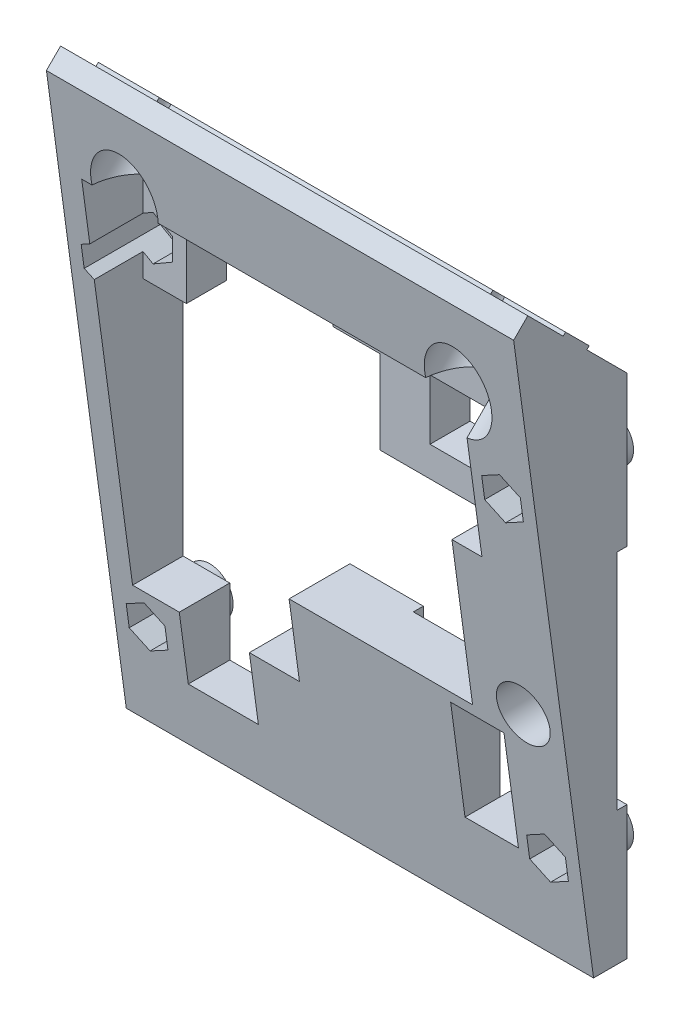
SolidWorks part; units mm, degrees
ref_plane "前视基准面" through (0, 0, 0) normal (0, 0, 1) x (1, 0, 0)
ref_plane "上视基准面" through (0, 0, 0) normal (0, 1, 0) x (1, 0, 0)
ref_plane "右视基准面" through (0, 0, 0) normal (1, 0, 0) x (0, 0, -1)
sketch "草图1" plane through (0, 0, 0) normal (1, 0, 0) x (0, 0, -1)
  line L0 (0, 0) -> (0, 76)
  line L1 (0, 76) -> (-14.8492, 90.8492)
  line L3 (-5, 0) -> (0, 0)
  line L4 (-14.8492, 90.8492) -> (-16.9706, 88.7279)
  line L5 (-16.9706, 88.7279) -> (-5, 0)
  dimension "D1" = 5
  dimension "D2" = 135
  dimension "D3" = 21
  dimension "D4" = 76
  dimension "D5" = 3
extrude "凸台-拉伸1" add sketch "草图1" along normal blind 90
sketch "草图2" plane through (0, 0, 0) normal (0, 0, -1) x (-1, 0, 0)
  line L0 (-90, 64) -> (0, 64) construction
  line L1 (-90, 0) -> (-90, 76) construction
  line L2 (0, 0) -> (0, 76) construction
  line L3 (-90, 14) -> (0, 14) construction
  line L4 (-75, 76) -> (-75, 0) construction
  line L5 (-90, 76) -> (0, 76) construction
  line L6 (-90, 0) -> (0, 0) construction
  line L7 (-15, 76) -> (-15, 0) construction
  circle A0 centre (-75, 64) radius 1.75
  circle A2 centre (-15, 64) radius 1.75
  circle A3 centre (-15, 14) radius 1.75
  circle A4 centre (-75, 14) radius 1.75
  dimension "D5" = 3.5
  dimension "D1" = 15
  dimension "D2" = 60
  dimension "D3" = 50
  dimension "D4" = 12
extrude "切除-拉伸1" cut sketch "草图2" against normal through all
sketch "草图3" plane through (0, 0, 0) normal (0, 0, -1) x (-1, 0, 0)
  line L0 (-90, 0) -> (-90, 76) construction
  line L1 (-38.5, 58) -> (-13.5, 58)
  line L2 (-38.5, 58) -> (-38.5, 19)
  line L3 (-38.5, 19) -> (-13.5, 19)
  line L4 (-13.5, 58) -> (-13.5, 19)
  line L5 (-20.5, 19) -> (-31, 19)
  line L6 (-20.5, 19) -> (-20.5, 9)
  line L7 (-20.5, 9) -> (-31, 9)
  line L8 (-31, 19) -> (-31, 9)
  line L9 (-20, 56) -> (-42, 56)
  line L10 (-20, 56) -> (-20, 67)
  line L11 (-20, 67) -> (-42, 67)
  line L12 (-42, 56) -> (-42, 67)
  line L13 (-49, 66) -> (-38, 66)
  line L14 (-49, 66) -> (-49, 53.5)
  line L15 (-49, 53.5) -> (-38, 53.5)
  line L16 (-38, 66) -> (-38, 53.5)
  line L17 (-70.5, 67) -> (-56.5, 67)
  line L18 (-70.5, 67) -> (-70.5, 58)
  line L19 (-70.5, 58) -> (-56.5, 58)
  line L20 (-56.5, 67) -> (-56.5, 58)
  line L21 (-90, 55) -> (-80.5, 55)
  line L22 (-90, 55) -> (-90, 13)
  line L23 (-90, 13) -> (-80.5, 13)
  line L24 (-80.5, 55) -> (-80.5, 13)
  line L25 (-90, 0) -> (0, 0) construction
  line L26 (-70.5, 13) -> (-62.5, 13)
  line L27 (-70.5, 13) -> (-70.5, 29)
  line L28 (-70.5, 29) -> (-62.5, 29)
  line L29 (-62.5, 13) -> (-62.5, 29)
  line L30 (-66, 30.5) -> (-38.5, 30.5)
  line L31 (-66, 30.5) -> (-66, 53.5)
  line L32 (-66, 53.5) -> (-38.5, 53.5)
  line L33 (-38.5, 30.5) -> (-38.5, 53.5)
  line L34 (0, 0) -> (0, 76) construction
  circle A0 centre (-15, 64) radius 1.75 construction
  circle A1 centre (-15, 64) radius 1.75 construction
  circle A2 centre (-75, 64) radius 1.75 construction
  circle A3 centre (-75, 14) radius 1.75 construction
  circle A4 centre (-15, 14) radius 1.75 construction
  circle A5 centre (-75, 64) radius 1.75 construction
  circle A6 centre (-75, 14) radius 1.75 construction
  circle A7 centre (-15, 14) radius 1.75 construction
  circle A8 centre (-74, 33.5) radius 4
  line M40 (-90, 76) -> (-90, 0)
  dimension "D22" = 8
  dimension "D1" = 39
  dimension "D2" = 6
  dimension "D3" = 1.5
  dimension "D4" = 25
  dimension "D5" = 5.5
  dimension "D6" = 16
  dimension "D7" = 10
  dimension "D8" = 2
  dimension "D9" = 11
  dimension "D10" = 5
  dimension "D11" = 22
  dimension "D12" = 49
  dimension "D13" = 1
  dimension "D14" = 11
  dimension "D16" = 9
  dimension "D17" = 4.5
  dimension "D18" = 14
  dimension "D19" = 5.5
  dimension "D20" = 1
  dimension "D21" = 42
  dimension "D23" = 4.5
  dimension "D24" = 1
  dimension "D25" = 8
  dimension "D26" = 16
  dimension "D27" = 19.5
  dimension "D28" = 1
  dimension "D30" = 23
  dimension "D31" = 24
  dimension "D32" = 30.5
extrude "切除-拉伸2" cut sketch "草图3" against normal through all contours L24 L21 L23 M40 | L20 L17 L18 L19 | L16 L13 L14 L15 | L12 L9 L2 L1 L10 L11 | L10 L9 L2 L3 L4 L1 | L9 L10 L1 L2 | L30 L33 L32 L31 | L3 L8 L7 L6 | L26 L29 L28 L27 | A8 | L16 L9 L2 L15 | L16 L1 L2 L9 | L16 L13 L12 L9 L2 L1 region at (40.0449, 61.1026, 0) region at (38.25, 57, 0) region at (29.2651, 62.5964, 0) region at (29, 57, 0) region at (38.25, 54.75, 0) region at (45.0227, 59.2955, 0) region at (25.8553, 37.7476, 0) region at (52.25, 42, 0) region at (25.75, 14, 0) region at (63.5, 62.5, 0) region at (85.25, 34, 0) region at (66.5, 21, 0) region at (74, 33.5, 0)
sketch "草图4" plane through (0, 0, 0) normal (0, 0, -1) x (-1, 0, 0)
  line L0 (-90, 0) -> (-90, 13) construction
  line L1 (-75, 60.6514) -> (-72.1, 62.3257)
  line L2 (-72.1, 62.3257) -> (-72.1, 65.6743)
  line L3 (-72.1, 65.6743) -> (-75, 67.3486)
  line L4 (-75, 67.3486) -> (-77.9, 65.6743)
  line L5 (-77.9, 65.6743) -> (-77.9, 62.3257)
  line L6 (-77.9, 62.3257) -> (-75, 60.6514)
  line L7 (-15, 60.6514) -> (-12.1, 62.3257)
  line L8 (-12.1, 62.3257) -> (-12.1, 65.6743)
  line L9 (-12.1, 65.6743) -> (-15, 67.3486)
  line L10 (-15, 67.3486) -> (-17.9, 65.6743)
  line L11 (-17.9, 65.6743) -> (-17.9, 62.3257)
  line L12 (-17.9, 62.3257) -> (-15, 60.6514)
  line L13 (-15, 10.6514) -> (-12.1, 12.3257)
  line L14 (-12.1, 12.3257) -> (-12.1, 15.6743)
  line L15 (-12.1, 15.6743) -> (-15, 17.3486)
  line L16 (-15, 17.3486) -> (-17.9, 15.6743)
  line L17 (-17.9, 15.6743) -> (-17.9, 12.3257)
  line L18 (-17.9, 12.3257) -> (-15, 10.6514)
  line L19 (-75, 10.6514) -> (-72.1, 12.3257)
  line L20 (-72.1, 12.3257) -> (-72.1, 15.6743)
  line L21 (-72.1, 15.6743) -> (-75, 17.3486)
  line L22 (-75, 17.3486) -> (-77.9, 15.6743)
  line L23 (-77.9, 15.6743) -> (-77.9, 12.3257)
  line L24 (-77.9, 12.3257) -> (-75, 10.6514)
  circle A4 centre (-75, 64) radius 2.9 construction
  circle A5 centre (-15, 64) radius 2.9 construction
  circle A6 centre (-15, 14) radius 2.9 construction
  circle A7 centre (-75, 14) radius 2.9 construction
  dimension "D1" = 5.8
extrude "切除-拉伸3" cut sketch "草图4" against normal up to next from offset 2 offset against normal yes
sketch "草图5" plane through (0, 0, 0) normal (0, 0, -1) x (-1, 0, 0)
  line L0 (-70.5, 13) -> (-70.5, 29) construction
  line L1 (-70.5, 30) -> (-80.5, 30)
  line L2 (-70.5, 30) -> (-70.5, 20)
  line L3 (-70.5, 20) -> (-80.5, 20)
  line L4 (-80.5, 30) -> (-80.5, 20)
  line L5 (-80.5, 55) -> (-80.5, 13) construction
  line L6 (-90, 0) -> (0, 0) construction
  line L7 (-80.5, 30) -> (-66, 30)
  line L8 (-80.5, 30) -> (-80.5, 53.5)
  line L9 (-80.5, 53.5) -> (-66, 53.5)
  line L10 (-66, 30) -> (-66, 53.5)
  line L11 (-62.5, 29) -> (-49.5, 29)
  line L12 (-62.5, 29) -> (-62.5, 0)
  line L13 (-62.5, 0) -> (-49.5, 0)
  line L14 (-49.5, 29) -> (-49.5, 0)
  line L15 (-66, 30.5) -> (-38.5, 30.5) construction
  line L16 (-70.5, 29) -> (-49.5, 29)
  line L17 (-70.5, 29) -> (-70.5, 30.5)
  line L18 (-70.5, 30.5) -> (-49.5, 30.5)
  line L19 (-49.5, 29) -> (-49.5, 30.5)
  circle A0 centre (-75, 14) radius 1.75 construction
  circle A1 centre (-75, 14) radius 1.75 construction
  circle M3 centre (-74, 33.5) radius 4
  line M4 (-62.5, 29) -> (-62.5, 13)
  line M6 (-70.5, 13) -> (-70.5, 29)
  line M14 (-66, 30.5) -> (-66, 53.5)
  line M16 (-80.5, 55) -> (-80.5, 13)
  line M19 (-90, 0) -> (0, 0)
  dimension "D1" = 10
  dimension "D2" = 6
  dimension "D3" = 13
extrude "切除-拉伸4" cut sketch "草图5" against normal blind 1.5 contours L7 L10 L9 L1 M14 M16 M3 | L3 L2 L1 M6 M3 M16 | L14 L11 L12 M4 M19 | L19 L18 L17 L16 region at (75.5199, 24.9364, 0) region at (73.162, 43.2176, 0) region at (56, 14.5, 0)
sketch "草图6" plane through (0, 38, -38) normal (0, 0.7071, -0.7071) x (1, 0, 0)
  line L0 (0, -53.7401) -> (0, -74.7401) construction
  line L1 (0, -62.2401) -> (90, -62.2401)
  line L2 (0, -62.2401) -> (0, -67.2401)
  line L3 (0, -67.2401) -> (90, -67.2401)
  line L4 (90, -62.2401) -> (90, -67.2401)
  line L5 (90, -53.7401) -> (90, -74.7401) construction
  line L6 (0, -64.7401) -> (90, -64.7401) construction
  line L7 (90, -74.7401) -> (0, -74.7401) construction
  dimension "D1" = 10
  dimension "D2" = 5
extrude "凸台-拉伸2" add sketch "草图6" along normal blind 0.5
sketch "草图7" plane through (0, 38.3536, -38.3536) normal (0, 0.7071, -0.7071) x (1, 0, 0)
  line L0 (0, -64.7401) -> (90, -64.7401) construction
  line L1 (0, -62.2401) -> (0, -67.2401) construction
  line L2 (90, -67.2401) -> (90, -62.2401) construction
  line L3 (0, -67.2401) -> (0, -74.7401) construction
  line L4 (90, -67.2401) -> (90, -74.7401) construction
  circle A0 centre (20, -64.7401) radius 2.65
  circle A1 centre (70, -64.7401) radius 2.65
  dimension "D1" = 5.3
  dimension "D2" = 20
  dimension "D3" = 20
extrude "切除-拉伸5" cut sketch "草图7" against normal through all
sketch "草图8" plane through (0, 38.3536, -38.3536) normal (0, 0.7071, -0.7071) x (1, 0, 0)
  circle A0 centre (20, -64.7401) radius 5
  circle A1 centre (70, -64.7401) radius 5
  dimension "D1" = 10
extrude "切除-拉伸6" cut sketch "草图8" against normal up to next from offset 4 offset against normal yes
sketch "草图9" plane through (0, 0, 0) normal (0, 0, -1) x (-1, 0, 0)
  circle A0 centre (-75, 64) radius 3.5
  circle A1 centre (-15, 64) radius 3.5
  circle A2 centre (-15, 14) radius 3.5
  circle A3 centre (-75, 14) radius 3.5
  dimension "D1" = 7
extrude "凸台-拉伸3" add sketch "草图9" along normal blind 2.5
sketch "草图10" plane through (0, 0, -2.5) normal (0, 0, -1) x (-1, 0, 0)
  circle A1 centre (-75, 14) radius 1.75
  circle A2 centre (-75, 14) radius 1.75
  circle A3 centre (-15, 14) radius 1.75
  circle A4 centre (-15, 14) radius 1.75
  circle A5 centre (-15, 64) radius 1.75
  circle A6 centre (-15, 64) radius 1.75
  circle A7 centre (-75, 64) radius 1.75
  circle A8 centre (-75, 64) radius 1.75
  dimension "D1" = 0
  dimension "D2" = 0
  dimension "D3" = 0
  dimension "D4" = 0
extrude "切除-拉伸7" cut sketch "草图10" against normal through all
sketch "草图11" plane through (0, 0, 0) normal (0, 0, -1) x (-1, 0, 0)
  line L0 (-70.5, 67) -> (-70.5, 58) construction
  line L1 (-13.5, 75.5) -> (-70.5, 75.5)
  line L2 (-13.5, 75.5) -> (-13.5, 53.5)
  line L3 (-13.5, 53.5) -> (-70.5, 53.5)
  line L4 (-70.5, 75.5) -> (-70.5, 53.5)
  line L5 (-66, 53.5) -> (-49, 53.5) construction
  line L6 (-13.5, 58) -> (-13.5, 19) construction
  dimension "D1" = 22
extrude "切除-拉伸8" cut sketch "草图11" against normal up to next from offset 6 offset against normal yes
sketch "草图12" plane through (0, -0.6625, 4.9106) normal (0, -0.1337, 0.991) x (1, 0, 0)
  line L0 (90, 90.2003) -> (90, 56.1668) construction
  line L1 (0, 94.5051) -> (10, 94.5051)
  line L2 (0, 94.5051) -> (0, -3.84)
  line L3 (0, -3.84) -> (10, -3.84)
  line L4 (10, 94.5051) -> (10, -3.84)
  line L5 (90, 94.5051) -> (80, 94.5051)
  line L6 (90, 94.5051) -> (90, -6.5332)
  line L7 (90, -6.5332) -> (80, -6.5332)
  line L8 (80, 94.5051) -> (80, -6.5332)
  line L9 (0, 90.2003) -> (0, 0.6685) construction
  dimension "D1" = 10
  dimension "D2" = 10
extrude "切除-拉伸9" cut sketch "草图12" against normal through all
